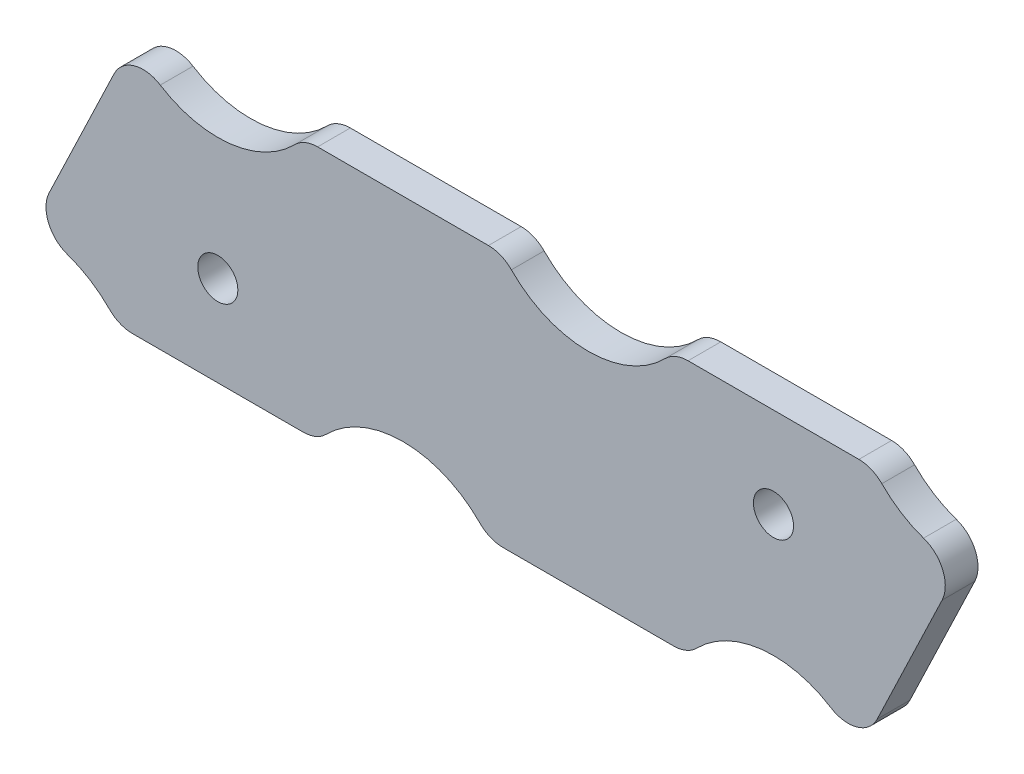
SolidWorks part; units mm, degrees
material "3003-H14"
ref_plane "X-Y Datum" through (0, 0, 0) normal (0, 0, 1) x (1, 0, 0)
ref_plane "X-Z Datum" through (0, 0, 0) normal (0, 1, 0) x (1, 0, 0)
ref_plane "Y-Z Datum" through (0, 0, 0) normal (1, 0, 0) x (0, 0, -1)
sketch "Sketch3" plane through (0, 0, 0) normal (0, 0, 1) x (1, 0, 0)
  line L0 (10.775, 10.775) -> (22.275, 34.775) construction
  line L1 (0, 0) -> (156.4633, 0) construction
  line L2 (0, 0) -> (0, 56.3098) construction
  line L3 (0, 56.3098) -> (156.4633, 56.3098) construction
  line L4 (156.4633, 0) -> (156.4633, 56.3098) construction
  line L5 (33.775, 10.775) -> (45.275, 34.775) construction
  line L6 (56.775, 10.775) -> (68.275, 34.775) construction
  line L7 (16.525, 22.775) -> (62.525, 22.775) construction
  line L8 (33.775, 10.775) -> (22.275, 34.775) construction
  line L9 (45.275, 34.775) -> (56.775, 10.775) construction
  line L10 (10.775, 10.775) -> (33.775, 10.775) construction
  line L11 (56.775, 10.775) -> (33.775, 10.775) construction
  line L12 (22.275, 34.775) -> (45.275, 34.775) construction
  line L13 (68.275, 34.775) -> (45.275, 34.775) construction
  line L14 (22.275, 34.775) -> (22.275, 10.775) construction
  line L15 (45.275, 10.775) -> (45.275, 34.775) construction
  line L16 (33.775, 10.775) -> (33.775, 34.775) construction
  line L17 (56.775, 34.775) -> (56.775, 10.775) construction
  line L18 (13.4804, 9.4786) -> (24.9804, 33.4786)
  line L19 (36.4804, 9.4786) -> (47.9804, 33.4786)
  line L20 (59.4804, 9.4786) -> (70.9804, 33.4786)
  line L21 (8.0696, 12.0714) -> (19.5696, 36.0714)
  line L22 (31.0696, 12.0714) -> (42.5696, 36.0714)
  line L23 (54.0696, 12.0714) -> (65.5696, 36.0714)
  line L24 (17.8152, 18.525) -> (57.1619, 18.525)
  line L25 (21.8881, 27.025) -> (61.2348, 27.025)
  line L26 (16.525, 27.025) -> (62.525, 27.025) construction
  line L27 (16.525, 18.525) -> (62.525, 18.525) construction
  line L28 (16.0692, 14.8813) -> (28.4808, 14.8813)
  line L29 (39.9808, 30.6687) -> (27.5692, 30.6687)
  line L48 (56.775, 10.775) -> (68.275, 10.775) construction
  line L49 (68.275, 10.775) -> (68.275, 34.775) construction
  line L50 (62.9808, 30.6687) -> (50.5692, 30.6687)
  line L51 (39.0692, 14.8813) -> (51.4808, 14.8813)
  circle A0 centre (10.775, 10.775) radius 10.775 construction
  circle A1 centre (33.775, 10.775) radius 10.775 construction
  circle A2 centre (22.275, 34.775) radius 10.775 construction
  circle A3 centre (45.275, 34.775) radius 10.775 construction
  circle A4 centre (68.275, 34.775) radius 10.775 construction
  circle A5 centre (56.775, 10.775) radius 10.775 construction
  circle A6 centre (10.775, 10.775) radius 4.7 construction
  circle A7 centre (33.775, 10.775) radius 4.7 construction
  circle A8 centre (56.775, 10.775) radius 4.7 construction
  circle A9 centre (68.275, 34.775) radius 4.7 construction
  circle A10 centre (45.275, 34.775) radius 4.7 construction
  circle A11 centre (22.275, 34.775) radius 4.7 construction
  circle A12 centre (22.275, 34.775) radius 6.7
  circle A13 centre (10.775, 10.775) radius 6.7
  circle A14 centre (33.775, 10.775) radius 6.7
  circle A15 centre (45.275, 34.775) radius 6.7
  circle A16 centre (68.275, 34.775) radius 6.7
  circle A17 centre (56.775, 10.775) radius 6.7
  circle A18 centre (125.775, 10.775) radius 10.775 construction
  circle A19 centre (102.775, 10.775) radius 10.775 construction
  circle A20 centre (79.775, 10.775) radius 10.775 construction
  circle A21 centre (91.275, 34.775) radius 10.775 construction
  circle A22 centre (114.275, 34.775) radius 10.775 construction
  circle A23 centre (137.275, 34.775) radius 10.775 construction
  dimension "D1" = 21.55
  dimension "D9" = 9.4
  dimension "D2" = 23
  dimension "D3" = 24
  dimension "D4" = 11.5
  dimension "D6" = 23
  dimension "D8" = 23
  dimension "D10" = 3
  dimension "D11" = 3
  dimension "D12" = 4.25
  dimension "D13" = 4.25
  dimension "D14" = 2
  dimension "D5" = 6
  dimension "D7" = 5
extrude "Boss-Extrude1" add sketch "Sketch3" along normal blind 2.032 contours L17 | L17 | L17 | L17 | L49 | A13 L18 A12 L21 | L25 L18 L24 L22 | L25 L22 L24 L19 | L25 L19 L24 L23 | A17 L20 A16 L23 | A14 L19 L24 L22 | A15 L22 L25 L19 | A14 L22 L24 L18 L28 | A12 L18 L25 L22 L29 | A17 L23 L24 L19 L51 | A15 L19 L25 L23 L50 region at (16.525, 22.775, 0) region at (24.1977, 16.8116, 0) region at (28.025, 22.775, 0) region at (31.8523, 28.7384, 0) region at (37.7051, 17.4114, 0) region at (39.525, 22.775, 0) region at (41.3449, 28.1386, 0) region at (47.1977, 16.8116, 0) region at (51.025, 22.775, 0) region at (54.8523, 28.7384, 0) region at (62.525, 22.775, 0)
ref_plane "Plane1" through (68.275, 0, 0) normal (1, 0, 0) x (0, 0, -1)
fillet "Fillet1" radius 2 12 edges at (62.9808, 30.6687, 1.016) (50.5692, 30.6687, 1.016) (39.9808, 30.6687, 1.016) (27.5692, 30.6687, 1.016) (16.0692, 14.8813, 1.016) (28.4808, 14.8813, 1.016) (39.0692, 14.8813, 1.016) (51.4808, 14.8813, 1.016) (68.3917, 28.076, 1.016) (62.0692, 14.8813, 1.016) (10.6583, 17.474, 1.016) (16.9808, 30.6687, 1.016)
sketch "Sketch4" plane through (0, 0, 2.032) normal (0, 0, 1) x (1, 0, 0)
  circle A0 centre (22.275, 20.4921) radius 1.2446
  circle A1 centre (56.775, 25.0579) radius 1.2446
  point P0 (56.775, 25.0579)
  point P1 (22.275, 20.4921)
  dimension "D1" = 2.4892
extrude "Cut-Extrude1" cut sketch "Sketch4" against normal through all
